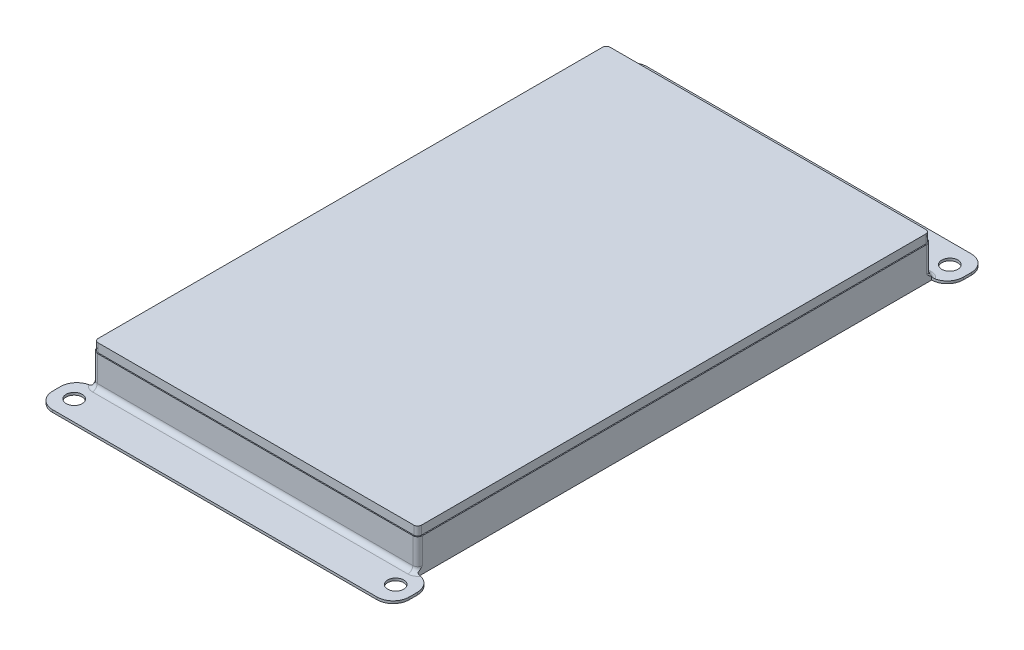
SolidWorks part; units mm, degrees
ref_plane "前视基准面" through (0, 0, 0) normal (0, 0, 1) x (1, 0, 0)
ref_plane "上视基准面" through (0, 0, 0) normal (0, 1, 0) x (1, 0, 0)
ref_plane "右视基准面" through (0, 0, 0) normal (1, 0, 0) x (0, 0, -1)
other "Configuration Table"
sketch "草图1" plane through (0, 0, 0) normal (0, 1, 0) x (1, 0, 0)
  line L0 (66.3853, -4.125) -> (69.6, -4.125)
  line L1 (-3.6, 4.125) -> (69.6, 4.125)
  line L2 (-3.6, 4.125) -> (-3.6, -4.125)
  line L3 (-3.6, -4.125) -> (-0.3853, -4.125)
  line L4 (69.6, 4.125) -> (69.6, -4.125)
  line L6 (-0.3853, -4.125) -> (-0.3853, -109.625)
  line L8 (66.3853, -4.125) -> (66.3853, -109.625)
  line L9 (-3.6, -109.625) -> (-0.3853, -109.625)
  line L10 (-3.6, -109.625) -> (-3.6, -117.875)
  line L11 (-3.6, -117.875) -> (69.6, -117.875)
  line L12 (69.6, -109.625) -> (69.6, -117.875)
  line L13 (66.3853, -109.625) -> (69.6, -109.625)
  line L14 (69.6, -113.75) -> (-3.6, -113.75) construction
  line L15 (-3.6, 0) -> (69.6, 0) construction
  line L16 (33, 4.125) -> (33, -117.875) construction
  line L17 (-0.3853, -56.875) -> (66.3853, -56.875) construction
  circle A2 centre (0, 0) radius 1.65
  circle A4 centre (66, 0) radius 1.65
  circle A5 centre (66, -113.75) radius 1.65
  circle A6 centre (0, -113.75) radius 1.65
  dimension "D4" = 3.3
  dimension "D1" = 122
  dimension "D2" = 66
  dimension "D3" = 66.7706
  dimension "D5" = 73.2
  dimension "D6" = 105.5
extrude "凸台-拉伸1" add sketch "草图1" along normal blind 0.5
fillet "圆角1" radius 3.3 8 edges at (69.6, 0.25, 109.625) (69.6, 0.25, 117.875) (-3.6, 0.25, 109.625) (-3.6, 0.25, 117.875) (-3.6, 0.25, 4.125) (-3.6, 0.25, -4.125) (69.6, 0.25, 4.125) (69.6, 0.25, -4.125)
sketch "草图2" plane through (0, 0, 0) normal (0, 1, 0) x (1, 0, 0)
  line L1 (-0.3853, -4.125) -> (66.3853, -4.125)
  line L2 (-0.3853, -4.125) -> (-0.3853, -109.625)
  line L3 (-0.3853, -109.625) -> (66.3853, -109.625)
  line L4 (66.3853, -4.125) -> (66.3853, -109.625)
extrude "凸台-拉伸2" add sketch "草图2" along normal blind 6.83
fillet "圆角2" radius 1 4 edges at (66.3853, 3.665, 4.125) (-0.3853, 3.665, 4.125) (-0.3853, 3.665, 109.625) (66.3853, 3.665, 109.625)
sketch "草图3" plane through (0, 6.83, 0) normal (0, 1, 0) x (1, 0, 0)
  line L8 (66.1853, -108.625) -> (66.1853, -5.125)
  line L9 (65.3853, -4.325) -> (0.6147, -4.325)
  line L10 (-0.1853, -5.125) -> (-0.1853, -108.625)
  line L11 (0.6147, -109.425) -> (65.3853, -109.425)
  line L12 (66.1853, -108.625) -> (66.1853, -5.125)
  line L13 (65.3853, -4.325) -> (0.6147, -4.325)
  line L14 (-0.1853, -5.125) -> (-0.1853, -108.625)
  line L15 (0.6147, -109.425) -> (65.3853, -109.425)
  arc A8 (66.1853, -5.125) -> (65.3853, -4.325) centre (65.3853, -5.125) ccw
  arc A9 (0.6147, -4.325) -> (-0.1853, -5.125) centre (0.6147, -5.125) ccw
  arc A10 (-0.1853, -108.625) -> (0.6147, -109.425) centre (0.6147, -108.625) ccw
  arc A11 (65.3853, -109.425) -> (66.1853, -108.625) centre (65.3853, -108.625) ccw
  arc A12 (66.1853, -5.125) -> (65.3853, -4.325) centre (65.3853, -5.125) ccw
  arc A13 (0.6147, -4.325) -> (-0.1853, -5.125) centre (0.6147, -5.125) ccw
  arc A14 (-0.1853, -108.625) -> (0.6147, -109.425) centre (0.6147, -108.625) ccw
  arc A15 (65.3853, -109.425) -> (66.1853, -108.625) centre (65.3853, -108.625) ccw
  dimension "D1" = 0.2
extrude "凸台-拉伸3" add sketch "草图3" along normal blind 1.78
fillet "圆角3" radius 1 6 edges at (66.0924, 0.5, 109.3321) (-0.0924, 0.5, 109.3321) (-0.0924, 0.5, 4.4179) (66.0924, 0.5, 4.4179) (33, 0.5, 109.625) (33, 0.5, 4.125)
